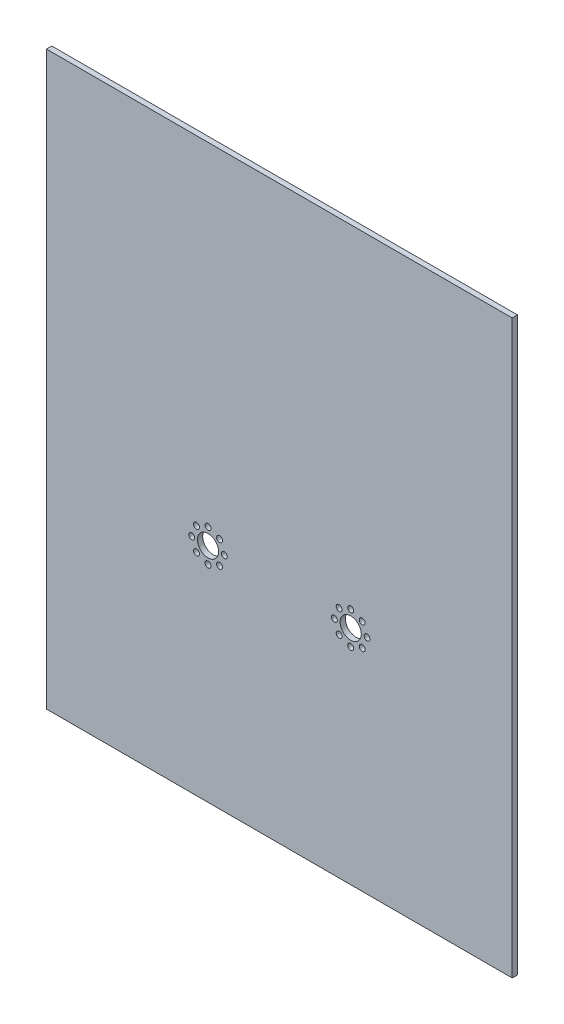
SolidWorks part; units mm, degrees
material "6061-T6 (SS)"
ref_plane "Front Plane" through (0, 0, 0) normal (0, 0, 1) x (1, 0, 0)
ref_plane "Top Plane" through (0, 0, 0) normal (0, 1, 0) x (1, 0, 0)
ref_plane "Right Plane" through (0, 0, 0) normal (1, 0, 0) x (0, 0, -1)
sketch "Sketch1" plane through (0, 0, 0) normal (0, 0, 1) x (1, 0, 0)
  line L1 (0, 0) -> (-279.4, 0)
  line L2 (0, 0) -> (0, -342.9)
  line L3 (0, -342.9) -> (-279.4, -342.9)
  line L4 (-279.4, 0) -> (-279.4, -342.9)
  dimension "D1" = 342.9
  dimension "D2" = 279.4
extrude "Boss-Extrude1" add sketch "Sketch1" along normal blind 3.175
sketch "Sketch2" plane through (0, 0, 0) normal (0, 0, -1) x (-1, 0, 0)
  line L0 (0, -209.55) -> (279.4, -209.55) construction
  line L1 (0, -342.9) -> (0, 0) construction
  line L2 (279.4, 0) -> (279.4, -342.9) construction
  line L3 (279.4, -342.9) -> (0, -342.9) construction
  circle A0 centre (87.122, -209.55) radius 1.778
  point P12 (96.901, -209.55)
  dimension "D2" = 96.901
  dimension "D3" = 3.556
  dimension "D1" = 133.35
  dimension "D5" = 9.779
extrude "Cut-Extrude1" cut sketch "Sketch2" against normal blind 3.175
ref_plane "Plane1" through (-139.7, 0, 0) normal (1, 0, 0) x (0, 0, -1)
mirror "Mirror1" about plane through (-139.7, 0, 0) normal (1, 0, 0) of "Cut-Extrude1"
sketch "Sketch3" plane through (0, 0, 0) normal (0, 0, -1) x (-1, 0, 0)
  line L2 (279.4, -342.9) -> (0, -342.9) construction
  line L3 (0, -342.9) -> (0, 0) construction
  circle A0 centre (96.901, -209.55) radius 6.35
  point P7 (0, 0)
  dimension "D3" = 12.7
  dimension "D1" = 133.35
  dimension "D2" = 96.901
extrude "Cut-Extrude2" cut sketch "Sketch3" against normal blind 3.175 contours A0
pattern_circular "CirPattern1" count 8 over 360 about axis through (-96.901, -209.55, 0) along (0, 0, -1) of "Cut-Extrude1"
mirror "Mirror2" about plane through (-139.7, 0, 0) normal (1, 0, 0) of "Cut-Extrude2", "CirPattern1"
